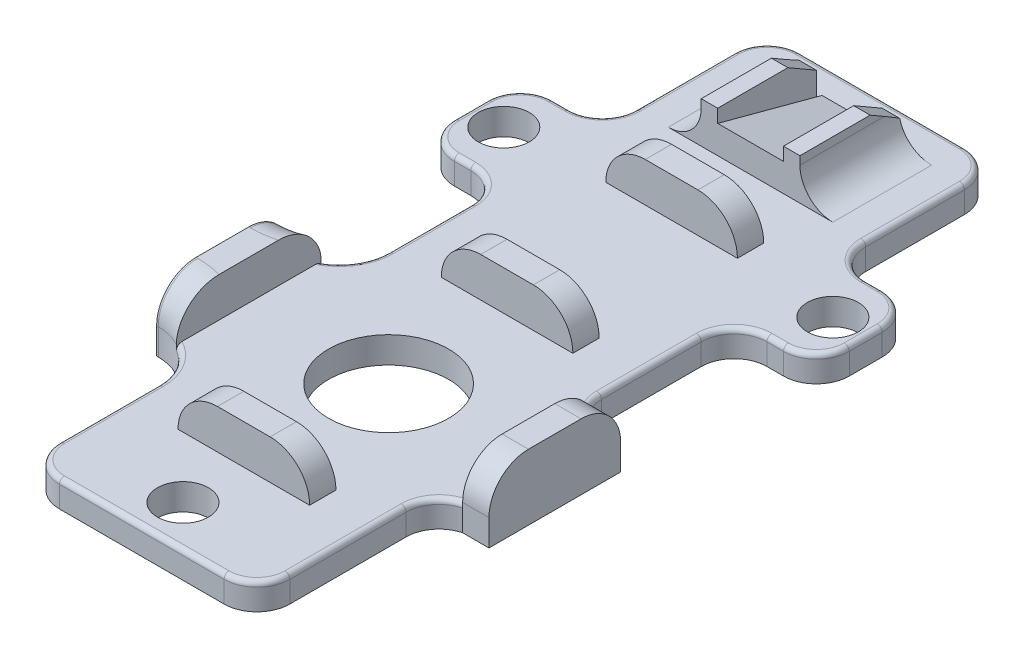
SolidWorks part; units mm, degrees
ref_plane "Front Plane" through (0, 0, 0) normal (0, 0, 1) x (1, 0, 0)
ref_plane "Top Plane" through (0, 0, 0) normal (0, 1, 0) x (1, 0, 0)
ref_plane "Right Plane" through (0, 0, 0) normal (1, 0, 0) x (0, 0, -1)
sketch "Sketch1" plane through (0, 0, 0) normal (0, 1, 0) x (1, 0, 0)
  line L1 (-7, -15) -> (7, -15)
  line L2 (-7, -15) -> (-7, 30)
  line L3 (-7, 30) -> (7, 30)
  line L4 (7, -15) -> (7, 30)
  line L5 (-7, -15) -> (7, 30) construction
  line L6 (-7, 30) -> (7, -15) construction
  point P0 (0, 7.5)
  dimension "D1" = 15
  dimension "D2" = 30
  dimension "D3" = 14
extrude "Boss-Extrude1" add sketch "Sketch1" along normal blind 1.6
sketch "Sketch2" plane through (0, 0, 0) normal (0, 1, 0) x (1, 0, 0)
  circle A0 centre (0, 0) radius 3.65
  dimension "D1" = 7.3
extrude "Cut-Extrude1" cut sketch "Sketch2" along normal through all
sketch "Sketch3" plane through (0, 0, 0) normal (0, -1, 0) x (1, 0, 0)
  line L0 (-7, 15) -> (7, 15) construction
  line L1 (2.5, 15) -> (-2.5, 15)
  line L2 (2.5, 15) -> (2.5, 14)
  line L3 (2.5, 14) -> (-2.5, 14)
  line L4 (-2.5, 15) -> (-2.5, 14)
  point P6 (0, 14)
  dimension "D1" = 1
  dimension "D2" = 5
extrude "Boss-Extrude2" [suppressed] add sketch "Sketch3" along normal blind 2.1
sketch "Sketch4" [suppressed] plane through (0, -2.1, 0) normal (0, -1, 0) x (1, 0, 0)
  line L0 (2.5, 14.2) -> (2.5, 15.2) construction
  line L1 (-2.5, 15.2) -> (2.5, 15.2)
  line L2 (-2.5, 15.2) -> (-2.5, 12.2)
  line L3 (-2.5, 12.2) -> (2.5, 12.2)
  line L4 (2.5, 15.2) -> (2.5, 12.2)
  dimension "D1" = 3
extrude "Boss-Extrude3" [suppressed] add sketch "Sketch4" along normal blind 1
sketch "Sketch5" plane through (0, 1.6, 0) normal (0, 1, 0) x (1, 0, 0)
  line L1 (-12, 14) -> (12, 14)
  line L2 (-12, 14) -> (-12, 20)
  line L3 (-12, 20) -> (12, 20)
  line L4 (12, 14) -> (12, 20)
  line L5 (-12, 14) -> (12, 20) construction
  line L6 (-12, 20) -> (12, 14) construction
  point P0 (0, 17)
  dimension "D1" = 6
  dimension "D2" = 24
  dimension "D3" = 17
extrude "Boss-Extrude4" add sketch "Sketch5" against normal up to vertex (1.6 mm away) up to point (-7, 0, -30)
sketch "Sketch6" plane through (0, 1.6, 0) normal (0, 1, 0) x (1, 0, 0)
  line L0 (12, 14) -> (12, 20) construction
  circle A0 centre (-10, 17) radius 1.55
  circle A1 centre (10, 17) radius 1.55
  circle A2 centre (0, -12.5) radius 1.55
  point P8 (12, 17)
  dimension "D2" = 3.1
  dimension "D1" = 10
  dimension "D3" = 10
  dimension "D4" = 12.5
extrude "Cut-Extrude2" cut sketch "Sketch6" against normal through all
sketch "Sketch10" plane through (7, 0, 0) normal (-1, 0, 0) x (0, 0, 1)
  line L0 (-14, 1.6) -> (15, 1.6) construction
  line L1 (4, 0) -> (-4, 0)
  line L2 (4, 0) -> (4, 1.6)
  line L3 (4, 1.6) -> (-4, 1.6)
  line L4 (-4, 0) -> (-4, 1.6)
  line L5 (4, 0) -> (-4, 1.6) construction
  line L6 (4, 1.6) -> (-4, 0) construction
  line L7 (-14, 0) -> (15, 0) construction
  point P0 (0, 0.8)
  dimension "D1" = 8
extrude "Boss-Extrude8" add sketch "Sketch10" against normal blind 1.5
sketch "Sketch11" plane through (8.5, 0, 0) normal (1, 0, 0) x (0, 0, -1)
  line L0 (-4, 1.6) -> (4, 1.6) construction
  line L1 (-1.3, 0) -> (1.3, 0)
  line L2 (-1.3, 0) -> (-1.3, 1.6)
  line L3 (-1.3, 1.6) -> (1.3, 1.6)
  line L4 (1.3, 0) -> (1.3, 1.6)
  line L5 (-1.3, 0) -> (1.3, 1.6) construction
  line L6 (-1.3, 1.6) -> (1.3, 0) construction
  line L7 (4, 0) -> (-4, 0) construction
  point P0 (0, 0.8)
  dimension "D1" = 2.6
extrude "Cut-Extrude3" cut sketch "Sketch11" against normal blind 1.1
fillet "Fillet1" radius 2 14 edges at (-7, 0.8, 15) (7, 0.8, 15) (7, 0.8, -30) (-7, 0.8, -30) (7, 0.8, -14) (12, 0.8, -14) (7, 0.8, -20) (12, 0.8, -20) (-7, 0.8, -20) (-12, 0.8, -20) (-7, 0.8, -14) (-12, 0.8, -14) (7, 0.8, -4) (7, 0.8, 4)
sketch "Sketch12" plane through (8.5, 0, 0) normal (1, 0, 0) x (0, 0, -1)
  line L1 (-4, 1.6) -> (4, 1.6)
  line L2 (-4, 1.6) -> (-4, 0)
  line L3 (-4, 0) -> (4, 0)
  line L4 (4, 1.6) -> (4, 0)
extrude "Boss-Extrude9" add sketch "Sketch12" along normal blind 1.6
sketch "Sketch13" plane through (-7, 0, 0) normal (-1, 0, 0) x (0, 0, 1)
  line L0 (-12, 1.6) -> (13, 1.6) construction
  line L1 (-4, 1.6) -> (4, 1.6)
  line L2 (-4, 1.6) -> (-4, 0)
  line L3 (-4, 0) -> (4, 0)
  line L4 (4, 1.6) -> (4, 0)
  line L5 (-12, 0) -> (13, 0) construction
  point P8 (0, 1.6)
  dimension "D1" = 8
extrude "Boss-Extrude10" add sketch "Sketch13" along normal blind 3.1
sketch "Sketch7" plane through (0, 1.6, 0) normal (0, 1, 0) x (1, 0, 0)
  line L0 (-4, 8.8) -> (-4, 7.2)
  line L1 (-4, 18.8) -> (4, 18.8)
  line L2 (-4, 18.8) -> (-4, 17.2)
  line L3 (-4, 17.2) -> (4, 17.2)
  line L4 (4, 18.8) -> (4, 17.2)
  line L5 (-4, 8.8) -> (4, 8.8)
  line L6 (4, 8.8) -> (4, 7.2)
  line L7 (-4, 7.2) -> (4, 7.2)
  line L8 (-4, -7.2) -> (-4, -8.8)
  line L9 (-4, -7.2) -> (4, -7.2)
  line L10 (4, -7.2) -> (4, -8.8)
  line L11 (-4, -8.8) -> (4, -8.8)
  line L13 (-8.5, 4) -> (-10.1, 4)
  line L14 (-8.5, 4) -> (-8.5, -4)
  line L15 (-8.5, -4) -> (-10.1, -4)
  line L16 (-10.1, 4) -> (-10.1, -4)
  line L17 (-8.5, 4) -> (-10.1, -4) construction
  line L18 (-8.5, -4) -> (-10.1, 4) construction
  line L19 (8.5, 4) -> (10.1, 4)
  line L20 (8.5, 4) -> (8.5, -4)
  line L21 (8.5, -4) -> (10.1, -4)
  line L22 (10.1, 4) -> (10.1, -4)
  line L23 (8.5, 4) -> (10.1, -4) construction
  line L24 (8.5, -4) -> (10.1, 4) construction
  point P4 (0, 17.2)
  point P6 (4, 18)
  point P7 (4, 8)
  point P12 (4, -8)
  point P17 (-9.3, 0)
  point P22 (9.3, 0)
  point P27 (0, 0)
  dimension "D1" = 1.6
  dimension "D2" = 8
  dimension "D3" = 18
  dimension "D5" = 10
  dimension "D7" = 26
  dimension "D8" = 9.3
  dimension "D9" = 9.3
  dimension "D4" = 2
  dimension "D6" = 2
extrude "Boss-Extrude5" add sketch "Sketch7" along normal blind 2.4
fillet "Fillet6" radius 3 2 edges at (-7, 0.8, -4) (-7, 0.8, 4)
fillet "Fillet2" radius 0.3 30 edges at (-7.5858, 1.6, -13.4142) (-11.4142, 1.6, -14.5858) (-12, 1.6, -17) (-11.4142, 1.6, -19.4142) (-7.5858, 1.6, -20.5858) (-7, 1.6, -25) (-6.4142, 1.6, -29.4142) (0, 1.6, -30) (6.4142, 1.6, -29.4142) (7, 1.6, -25) (7.5858, 1.6, -20.5858) (11.4142, 1.6, -19.4142) (12, 1.6, -17) (11.4142, 1.6, -14.5858) (7.5858, 1.6, -13.4142) (7, 1.6, -8.9682) (7, 1.6, 9.4682) (6.4142, 1.6, 14.4142) (0, 1.6, 15) (-6.4142, 1.6, 14.4142) (-7, 1.6, -9.5) (-7, 1.6, 10) (-9.5, 1.6, -14) (-9.5, 1.6, -20) (9.5, 1.6, -20) (9.5, 1.6, -14) (7.4189, 1.6, -4.7117) (7.4189, 1.6, 4.7117) (-7.4019, 1.6, -5.5) (-7.4019, 1.6, 5.5)
fillet "Fillet4" radius 2.4 12 edges at (4, 4, -18) (4, 4, -8) (-4, 4, -8) (-4, 4, -18) (4, 4, 8) (-4, 4, 8) (9.3, 4, -4) (9.3, 4, 4) (-10.05, 4, 4) (-10.05, 4, -4) (-9.2235, 4, 4.1022) (-9.2235, 4, -4.1022)
sketch "Sketch8" plane through (0, 1.6, 0) normal (0, 1, 0) x (1, 0, 0)
  line L1 (-3, 22) -> (3, 22)
  line L2 (-3, 22) -> (-3, 28)
  line L3 (-3, 28) -> (3, 28)
  line L4 (3, 22) -> (3, 28)
  line L5 (-3, 22) -> (3, 28) construction
  line L6 (-3, 28) -> (3, 22) construction
  line L7 (2, 22) -> (-2, 22)
  line L8 (2, 22) -> (2, 28)
  line L9 (2, 28) -> (-2, 28)
  line L10 (-2, 22) -> (-2, 28)
  line L11 (2, 22) -> (-2, 28) construction
  line L12 (2, 28) -> (-2, 22) construction
  point P0 (0, 25)
  point P5 (0, 25)
  dimension "D1" = 22
  dimension "D2" = 6
  dimension "D3" = 6
  dimension "D4" = 4
extrude "Boss-Extrude6" add sketch "Sketch8" along normal blind 2.5 contours L1 L10 L3 L2 | L8 L1 L4 L3 region at (-2.5, 1.6, -25) region at (2.5, 1.6, -25)
sketch "Sketch9" plane through (-2, 0, 0) normal (1, 0, 0) x (0, 0, -1)
  line L0 (22, 1.6) -> (28.3445, 1.6)
  line L1 (28.3445, 1.6) -> (22, 3.3)
  line L2 (22, 4.1) -> (22, 1.6) construction
  line L3 (22, 3.3) -> (22, 1.6)
  dimension "D1" = 15
  dimension "D2" = 1.7
extrude "Boss-Extrude7" add sketch "Sketch9" along normal up to vertex (4 mm away) up to point (2, 4.1, -22)
chamfer "Chamfer1" distance 1 angle 60 2 edges at (-2.5, 4.1, -28) (2.5, 4.1, -28) first distance on face at (-2.4, 2.6185, -28) first distance on face at (2.4, 2.6185, -28)
fillet "Fillet5" radius 2 2 edges at (3, 1.6, -25) (-3, 1.6, -25)
sketch "Sketch14" plane through (0, 0, 0) normal (0, -1, 0) x (1, 0, 0)
  line L1 (8.5, -1.3) -> (8.8, -1.3)
  line L2 (8.5, -1.3) -> (8.5, 1.3)
  line L3 (8.5, 1.3) -> (8.8, 1.3)
  line L4 (8.8, -1.3) -> (8.8, 1.3)
  point P5 (0, 0)
  point P6 (8.5, 1.3)
  dimension "D1" = 0.3
extrude "Cut-Extrude4" cut sketch "Sketch14" against normal blind 2
equation "\"D3@Sketch6\"=\"D1@Sketch6\""
